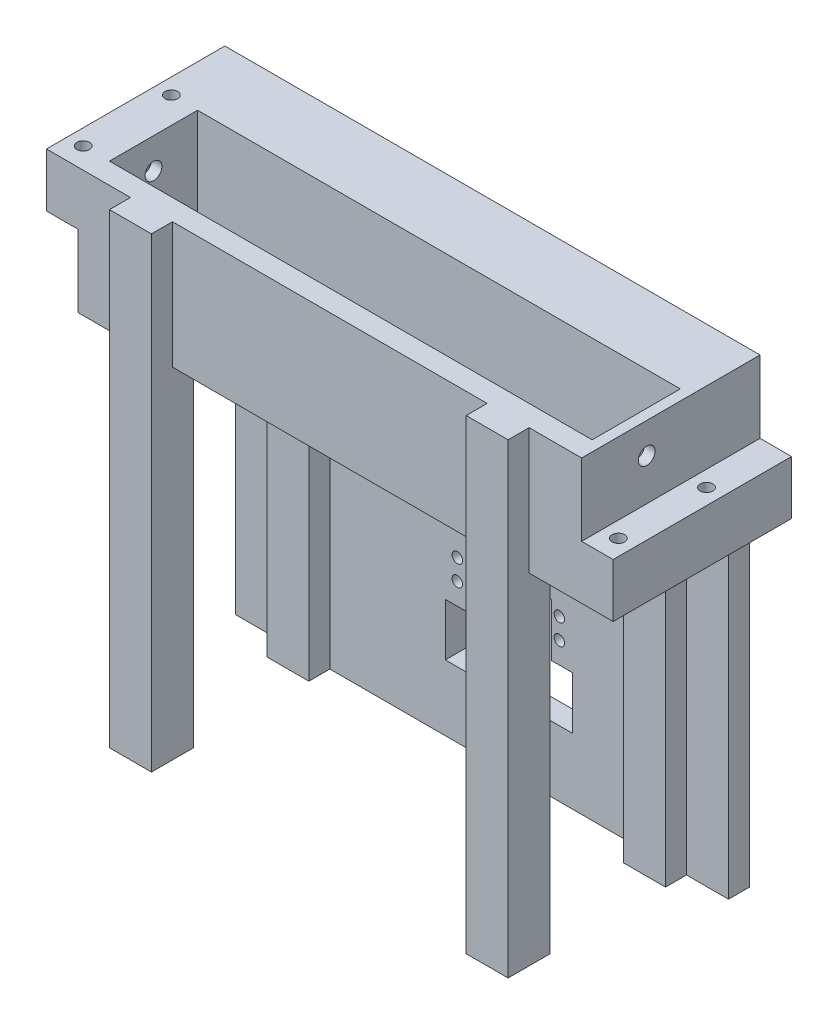
SolidWorks part; units mm, degrees
ref_plane "Front Plane" through (0, 0, 0) normal (0, 0, 1) x (1, 0, 0)
ref_plane "Top Plane" through (0, 0, 0) normal (0, 1, 0) x (1, 0, 0)
ref_plane "Right Plane" through (0, 0, 0) normal (1, 0, 0) x (0, 0, -1)
sketch "Sketch2" plane through (0, 0, 0) normal (0, 1, 0) x (1, 0, 0)
  line L2 (-125, 0) -> (-125, 21)
  line L3 (-125, 0) -> (-125, -21)
  line L4 (125, 0) -> (125, 21)
  line L5 (125, 0) -> (125, -21)
  line L6 (-115, 21) -> (115, 21)
  line L7 (-115, -21) -> (115, -21)
  line L8 (-125, 21) -> (-125, 31)
  line L9 (-125, 31) -> (125, 31)
  line L10 (125, 31) -> (125, 21)
  line L11 (-125, -21) -> (-125, -31)
  line L12 (-125, -31) -> (125, -31)
  line L13 (125, -31) -> (125, -21)
  line L14 (-125, 31) -> (-115, 31)
  line L15 (-115, 21) -> (-115, -21)
  line L16 (125, 31) -> (115, 31)
  line L17 (115, 21) -> (115, -21)
extrude "Boss-Extrude1" add sketch "Sketch2" along normal blind 60 contours L12 L13 L5 L4 L10 L9 L8 L2 L3 L11 L6 L17 L7 L15 region at (-122.4243, 0, -10.5)
sketch "Sketch4" plane through (0, 0, 0) normal (0, -1, 0) x (1, 0, 0)
  line L0 (125, 31) -> (-125, 31)
  line L1 (-125, 31) -> (-125, 21)
  line L3 (-115, 21) -> (125, 21)
  line L4 (125, 31) -> (125, -31) construction
  line L5 (125, 31) -> (125, 21)
  line L6 (-115, 21) -> (-125, 21)
extrude "Boss-Extrude2" add sketch "Sketch4" along normal blind 150
sketch "Sketch5" plane through (-125, 0, 0) normal (-1, 0, 0) x (0, 0, 1)
  circle A0 centre (0, 15.3956) radius 4
  circle A1 centre (0, 45.3956) radius 4
extrude "Cut-Extrude1" cut sketch "Sketch5" against normal blind 277
sketch "Sketch7" plane through (125, 0, 0) normal (1, 0, 0) x (0, 0, -1)
  line L0 (-21, -150) -> (-31, -150)
  line L1 (-31, -150) -> (-31, 60)
  line L2 (-31, 60) -> (31, 60)
  line L3 (31, 60) -> (31, 0)
  line L4 (31, 0) -> (-21, 0)
  line L5 (-21, 0) -> (-21, -150)
  circle A0 centre (0, 15.3956) radius 4
  circle A1 centre (0, 45.3956) radius 4
extrude "Boss-Extrude3" add sketch "Sketch7" against normal blind 20
extrude "Cut-Extrude2" cut sketch "Sketch7<2>" against normal blind 10
sketch "Sketch7<2>" plane through (125, 0, 0) normal (1, 0, 0) x (0, 0, -1) same geometry as "Sketch7"
sketch "Sketch8" plane through (115, 0, 0) normal (1, 0, 0) x (0, 0, -1)
  line L0 (-31, 60) -> (-31, -150) construction
  line L1 (-31, 0) -> (31, 0)
  line L2 (-31, 0) -> (-31, 24.6)
  line L3 (-31, 24.6) -> (31, 24.6)
  line L4 (31, 0) -> (31, 24.6)
  line L5 (31, 0) -> (31, 60) construction
extrude "Boss-Extrude4" add sketch "Sketch8" along normal blind 14
sketch "Sketch9" plane through (-125, 0, 0) normal (-1, 0, 0) x (0, 0, 1)
  line L0 (-31, 60) -> (-31, 0) construction
  line L1 (31, 60) -> (-31, 60)
  line L2 (31, 60) -> (31, 35.4)
  line L3 (31, 35.4) -> (-31, 35.4)
  line L4 (-31, 60) -> (-31, 35.4)
extrude "Boss-Extrude5" add sketch "Sketch9" along normal blind 14
sketch "Sketch13" plane through (-4.9991, -41.0467, 21) normal (0, 0, -1) x (-1, 0, 0)
  circle A0 centre (0, -50.4) radius 4.5
sketch "Sketch15" plane through (105, 0, 0) normal (-1, 0, 0) x (0, 0, 1)
  line L1 (-21, 0) -> (21, 0)
  line L2 (-21, 0) -> (-21, 60)
  line L3 (-21, 60) -> (21, 60)
  line L4 (21, 0) -> (21, 60)
  circle A0 centre (0, 15.3956) radius 4
  circle A1 centre (0, 45.3956) radius 4
extrude "Cut-Extrude3" cut sketch "Sketch15" against normal blind 5
sketch "Sketch17" plane through (-115, 0, 0) normal (1, 0, 0) x (0, 0, -1)
  line L1 (21, 0) -> (-21, 0)
  line L2 (21, 0) -> (21, 60)
  line L3 (21, 60) -> (-21, 60)
  line L4 (-21, 0) -> (-21, 60)
  circle A0 centre (0, 45.3956) radius 4
  circle A1 centre (0, 15.3956) radius 4
extrude "Cut-Extrude4" cut sketch "Sketch17" against normal blind 5
sketch "Sketch18" plane through (0, 35.4, 0) normal (0, -1, 0) x (1, 0, 0)
  line L0 (-140, 31) -> (-125, 31)
  line L2 (-125, 31) -> (-125, -31)
  line L4 (-125, -31) -> (-140, -31)
  line L8 (-140, 31) -> (-140, -31)
  line L11 (-139, 31) -> (-139, -31)
  circle A2 centre (-132.5, 21) radius 3
  circle A3 centre (-132.5, -21) radius 3
  line M11 (-139, 31) -> (-139, -31)
extrude "Boss-Extrude9" add sketch "Sketch18" against normal up to surface (24.6 mm away) contours L0 L8 L4 M11 region at (-139.5, 35.4, 0) up to face at (-5, 60, 0)
extrude "Cut-Extrude5" cut sketch "Sketch18<3>" against normal blind 35 contours A2 | A3 region at (-132.5, 35.4, 21) region at (-132.5, 35.4, -21)
sketch "Sketch18<3>" plane through (0, 35.4, 0) normal (0, -1, 0) x (1, 0, 0) same geometry as "Sketch18"
sketch "Sketch19" plane through (0, 24.6, 0) normal (0, 1, 0) x (1, 0, 0)
  line L0 (115, -31) -> (130, -31)
  line L1 (130, -31) -> (130, 31)
  line L2 (115, 31) -> (130, 31)
  line L3 (115, -31) -> (115, 31)
  line L4 (122.5, -31) -> (122.5, -21)
  line L5 (122.5, 31) -> (122.5, 21)
  line L6 (129, 31) -> (129, -31)
  circle A0 centre (122.5, 21) radius 3
  circle A1 centre (122.5, -21) radius 3
  line M8 (129, -31) -> (129, 31)
extrude "Boss-Extrude10" add sketch "Sketch19" against normal up to surface (24.6 mm away) contours L2 L0 L1 M8 region at (129.5, 24.6, 0) up to face at (21.8, 0, 4.2)
extrude "Cut-Extrude6" cut sketch "Sketch19<3>" against normal blind 27 contours A0 | A1 region at (120.4387, 24.6, 18.9387) region at (124.5613, 24.6, -23.0613)
sketch "Sketch19<3>" plane through (0, 24.6, 0) normal (0, 1, 0) x (1, 0, 0) same geometry as "Sketch19"
sketch "Sketch20" plane through (0, 24.6, 0) normal (0, 1, 0) x (1, 0, 0)
  line L1 (115, -31) -> (130, -31)
  line L2 (115, -31) -> (115, 31)
  line L3 (115, 31) -> (130, 31)
  line L4 (130, -31) -> (130, 31)
  circle A0 centre (122.5, -21) radius 3
  circle A1 centre (122.5, 21) radius 3
extrude "Boss-Extrude11" add sketch "Sketch20" along normal blind 1
sketch "Sketch21" plane through (0, 35.4, 0) normal (0, -1, 0) x (1, 0, 0)
  line L1 (-140, 31) -> (-125, 31)
  line L2 (-140, 31) -> (-140, -31)
  line L3 (-140, -31) -> (-125, -31)
  line L4 (-125, 31) -> (-125, -31)
  circle A0 centre (-132.5, 21) radius 3
  circle A1 centre (-132.5, -21) radius 3
extrude "Boss-Extrude12" add sketch "Sketch21" along normal blind 1
sketch "Sketch23" plane through (0, 0, 0) normal (0, -1, 0) x (1, 0, 0)
  line L0 (-125, 21) -> (-125, -31) construction
  line L1 (130, -31) -> (-125, -31)
  line L2 (130, -31) -> (130, -21)
  line L3 (130, -21) -> (-125, -21)
  line L4 (-125, -31) -> (-125, -21)
extrude "Boss-Extrude13" add sketch "Sketch23" along normal up to surface (150 mm away) up to face at (-5, -150, 26)
sketch "Sketch25" plane through (0, 0, 0) normal (0, -1, 0) x (1, 0, 0)
  line L1 (-130.2789, 16.1962) -> (121.1118, 16.1962)
  line L2 (-130.2789, 16.1962) -> (-130.2789, 38.4588)
  line L3 (-130.2789, 38.4588) -> (121.1118, 38.4588)
  line L4 (121.1118, 16.1962) -> (121.1118, 38.4588)
extrude "Cut-Extrude7" cut sketch "Sketch25" along normal up to surface (150 mm away) up to face at (-5, -150, 26)
sketch "Sketch26" plane through (0, 0, -31) normal (0, 0, -1) x (-1, 0, 0)
  line L1 (125, -150) -> (-130, -150)
  line L2 (125, -150) -> (125, 25.6)
  line L3 (-115, 25.6) -> (-130, 25.6)
  line L4 (-130, -150) -> (-130, 25.6)
  line L5 (-115, 60) -> (125, 60)
  line L6 (-115, 60) -> (-115, 25.6)
  line L8 (125, 34.4) -> (125, 25.6)
  line L9 (140, 34.4) -> (125, 34.4)
  line L10 (140, 34.4) -> (140, 60)
  line L11 (140, 60) -> (125, 60)
extrude "Boss-Extrude16" add sketch "Sketch26" along normal blind 17
sketch "Sketch27" plane through (0, 0, 0) normal (0, -1, 0) x (1, 0, 0)
  line L1 (110, -31) -> (132.3474, -31)
  line L2 (132.3474, -31) -> (132.3474, -21)
  line L3 (132.3474, -21) -> (110, -21)
  line L4 (110, -31) -> (-153.4122, -31)
  line L5 (-153.4122, -31) -> (-153.4122, -21)
  line L6 (-153.4122, -21) -> (110, -21)
extrude "Cut-Extrude8" cut sketch "Sketch27" along normal up to surface (150 mm away) up to face at (2.5, -150, -34.5)
sketch "Sketch28" plane through (0, 0, 0) normal (0, -1, 0) x (1, 0, 0)
  line L0 (130, -31) -> (130, -44)
  line L1 (130, -44) -> (-125, -44)
  line L2 (-125, -31) -> (-125, -44)
  line L3 (-125, -31) -> (130, -31)
extrude "Cut-Extrude9" cut sketch "Sketch28" along normal blind 167
sketch "Sketch29" plane through (0, 0, -48) normal (0, 0, -1) x (-1, 0, 0)
  line L1 (125, -150) -> (-130, -150)
  line L2 (125, -150) -> (125, 25.6)
  line L3 (-115, 25.6) -> (-130, 25.6)
  line L4 (-130, -150) -> (-130, 25.6)
  line L5 (-115, 60) -> (125, 60)
  line L6 (-115, 60) -> (-115, 25.6)
  line L8 (125, 34.4) -> (125, 25.6)
  line L9 (140, 34.4) -> (125, 34.4)
  line L10 (140, 34.4) -> (140, 60)
  line L11 (140, 60) -> (125, 60)
extrude "Boss-Extrude18" add sketch "Sketch29" along normal blind 6
sketch "Sketch31" plane through (0, 0, -44) normal (0, 0, 1) x (1, 0, 0)
  line L0 (130, -150) -> (33.05, -150)
  line L1 (130, -150) -> (-125, -150) construction
  line L2 (-22.95, -100.63) -> (-125, -100.63)
  line L4 (-22.95, -100.63) -> (-22.95, -80.63)
  line L5 (33.05, -80.63) -> (33.05, -100.63)
  line L6 (-22.95, -80.63) -> (33.05, -80.63)
  line L7 (33.05, -100.63) -> (130, -100.63)
  line L8 (130, -150) -> (130, 0) construction
  line L9 (130, -100.63) -> (33.05, -100.63)
  line L10 (-125, -150) -> (-125, 0) construction
  line L11 (-125, -100.63) -> (-125, -150)
  line L12 (-125, -150) -> (130, -150)
  line L13 (130, -100.63) -> (130, -150)
  line L14 (130, -150) -> (130, -100.63)
  line M5 (130, -150) -> (130, 0)
  line M7 (-125, 0) -> (-125, -150)
  line M8 (-125, -150) -> (130, -150)
extrude "Cut-Extrude10" cut sketch "Sketch31" against normal blind 43 contours L7 L5 L6 L4 L2 M7 M8 M5 region at (2.7083, -122.4814, -44)
sketch "Sketch32" plane through (33.05, 0, 0) normal (-1, 0, 0) x (0, 0, 1)
  line L1 (-54, -100.63) -> (-44, -100.63)
  line L2 (-54, -100.63) -> (-54, -80.63)
  line L3 (-54, -80.63) -> (-44, -80.63)
  line L4 (-44, -100.63) -> (-44, -80.63)
extrude "Boss-Extrude19" add sketch "Sketch32" along normal blind 7.5
sketch "Sketch33" plane through (-22.95, 0, 0) normal (1, 0, 0) x (0, 0, -1)
  line L1 (54, -100.63) -> (44, -100.63)
  line L2 (54, -100.63) -> (54, -80.63)
  line L3 (54, -80.63) -> (44, -80.63)
  line L4 (44, -100.63) -> (44, -80.63)
extrude "Boss-Extrude20" add sketch "Sketch33" along normal blind 8
sketch "Sketch38" plane through (0, 0, -44) normal (0, 0, 1) x (1, 0, 0)
  circle A0 centre (29.35, -95.53) radius 2.5
  circle A1 centre (29.35, -85.73) radius 2.5
  circle A2 centre (-19.25, -95.53) radius 2.5
  circle A3 centre (-19.25, -85.73) radius 2.5
extrude "Cut-Extrude12" cut sketch "Sketch38" against normal blind 16
sketch "Sketch40" plane through (0, 0, 0) normal (0, -1, 0) x (1, 0, 0)
  line L1 (-125, -44) -> (130, -44) construction
  line L2 (89.9735, -44) -> (89.9735, -34)
  line L3 (89.9735, -34) -> (69.9735, -34)
  line L4 (69.9735, -34) -> (69.9735, -44)
  line L5 (69.9735, -44) -> (89.9735, -44)
  line L6 (-5, -21) -> (-5, -44)
  line L7 (110, -21) -> (-120, -21) construction
  line L8 (-79.9735, -44) -> (-99.9735, -44)
  line L9 (-79.9735, -34) -> (-79.9735, -44)
  line L10 (-99.9735, -34) -> (-79.9735, -34)
  line L11 (-99.9735, -44) -> (-99.9735, -34)
  line L13 (109.9735, -44) -> (130, -44)
  line L14 (109.9735, -44) -> (109.9735, -56.6663)
  line L15 (109.9735, -56.6663) -> (130, -56.6663)
  line L16 (130, -44) -> (130, -56.6663)
  line M13 (-125, -44) -> (130, -44)
extrude "Cut-Extrude13" cut sketch "Sketch40" along normal blind 116 contours L16 L14 L15 M13 region at (119.9867, 0, -50.3331)
sketch "Sketch41" plane through (0, -100.63, 0) normal (0, -1, 0) x (1, 0, 0)
  line L1 (109.9735, -54) -> (25.55, -54)
  line L2 (109.9735, -54) -> (109.9735, -44)
  line L3 (109.9735, -44) -> (25.55, -44)
  line L4 (25.55, -54) -> (25.55, -44)
  line L5 (-14.95, -54) -> (-125, -54)
  line L6 (-14.95, -54) -> (-14.95, -44)
  line L7 (-14.95, -44) -> (-125, -44)
  line L8 (-125, -54) -> (-125, -44)
extrude "Boss-Extrude21" add sketch "Sketch41" along normal blind 61.47
sketch "Sketch42" plane through (25.55, 0, 0) normal (-1, 0, 0) x (0, 0, 1)
  line L0 (-44, -80.63) -> (-44, -105.7996)
  line L1 (-44, -162.1) -> (-44, -80.63) construction
  line L7 (-44, -105.7996) -> (-44, -130.7996)
  line L8 (-44, -130.7996) -> (-54, -130.7996)
  line L9 (-54, -80.63) -> (-54, -162.1) construction
  line L10 (-54, -130.7996) -> (-54, -105.7996)
  line L11 (-54, -105.7996) -> (-44, -105.7996)
extrude "Cut-Extrude14" cut sketch "Sketch42" against normal blind 10 contours L7 L8 L10 L11
ref_plane "Plane1" through (5.3, 0, 0) normal (-1, 0, 0) x (0, 0, 1)
mirror "Mirror1" about plane through (5.3, 0, 0) normal (-1, 0, 0) of "Cut-Extrude14"
extrude "Boss-Extrude22" add sketch "Sketch40<3>" along normal up to surface (162.1 mm away) contours L3 L4 L5 L2 | L10 L9 L8 L11 up to face at (67.7617, -162.1, -49)
sketch "Sketch40<3>" plane through (0, 0, 0) normal (0, -1, 0) x (1, 0, 0) same geometry as "Sketch40"
sketch "Sketch43" plane through (25.55, 0, 0) normal (-1, 0, 0) x (0, 0, 1)
  line L1 (-44, -162.1) -> (-54, -162.1)
  line L2 (-44, -162.1) -> (-44, -130.7996)
  line L3 (-44, -130.7996) -> (-54, -130.7996)
  line L4 (-54, -162.1) -> (-54, -130.7996)
extrude "Boss-Extrude23" add sketch "Sketch43" along normal up to surface (40.5 mm away) up to face at (-14.95, -146.4498, -49)
ref_plane "Plane2" through (0, 0, 0) normal (0, 0, -1) x (-1, 0, 0)
sketch "Sketch46" plane through (0, 0, 0) normal (0, -1, 0) x (1, 0, 0)
  line L5 (-120, 21) -> (110, 21) construction
  line L6 (89.9735, 21) -> (89.9735, 41)
  line L7 (89.9735, 41) -> (69.9735, 41)
  line L8 (69.9735, 41) -> (69.9735, 21)
  line L9 (69.9735, 21) -> (89.9735, 21)
  line L10 (-79.9735, 21) -> (-99.9735, 21)
  line L11 (-79.9735, 41) -> (-79.9735, 21)
  line L12 (-99.9735, 41) -> (-79.9735, 41)
  line L13 (-99.9735, 21) -> (-99.9735, 41)
extrude "Boss-Extrude24" add sketch "Sketch46" along normal up to surface (162.1 mm away) and the other way up to surface (60 mm away) up to face at (-5.8378, -162.1, -42.3333) other way up to face at (-132.5, 60, 24)
sketch "Sketch48" plane through (0, -162.1, 0) normal (0, -1, 0) x (1, 0, 0)
  line L0 (89.9735, 31) -> (69.9735, 31)
  line L1 (89.9735, 21) -> (89.9735, 41) construction
  line L2 (69.9735, 41) -> (69.9735, 21) construction
  line L3 (89.9735, -34) -> (89.9735, -54)
  line L4 (-125, -54) -> (109.9735, -54) construction
  line L5 (89.9735, -44) -> (79.9735, -44)
  line L6 (-79.9735, 31) -> (-99.9735, 31)
  line L7 (-79.9735, 21) -> (-79.9735, 41) construction
  line L8 (-99.9735, 41) -> (-99.9735, 21) construction
  line L9 (-89.9735, -34) -> (-89.9735, -54)
  line L10 (-99.9735, -34) -> (-79.9735, -34) construction
  circle A0 centre (79.9735, 31) radius 2
  circle A1 centre (79.9735, -44) radius 2
  circle A2 centre (-89.9735, 31) radius 2
  circle A3 centre (-89.9735, -44) radius 2
extrude "Cut-Extrude15" cut sketch "Sketch48" against normal blind 30 contours L0 A0 | L0 A0 | A1 | L6 A2 | L6 A2 | L9 A3 | L9 A3 region at (79.9735, -162.1, 30.1512) region at (79.9735, -162.1, 31.8488) region at (-89.9735, -162.1, 30.1512) region at (-89.9735, -162.1, 31.8488) region at (-89.1247, -162.1, -44) region at (-90.8223, -162.1, -44) region at (78.0301, -162.1, -44)
